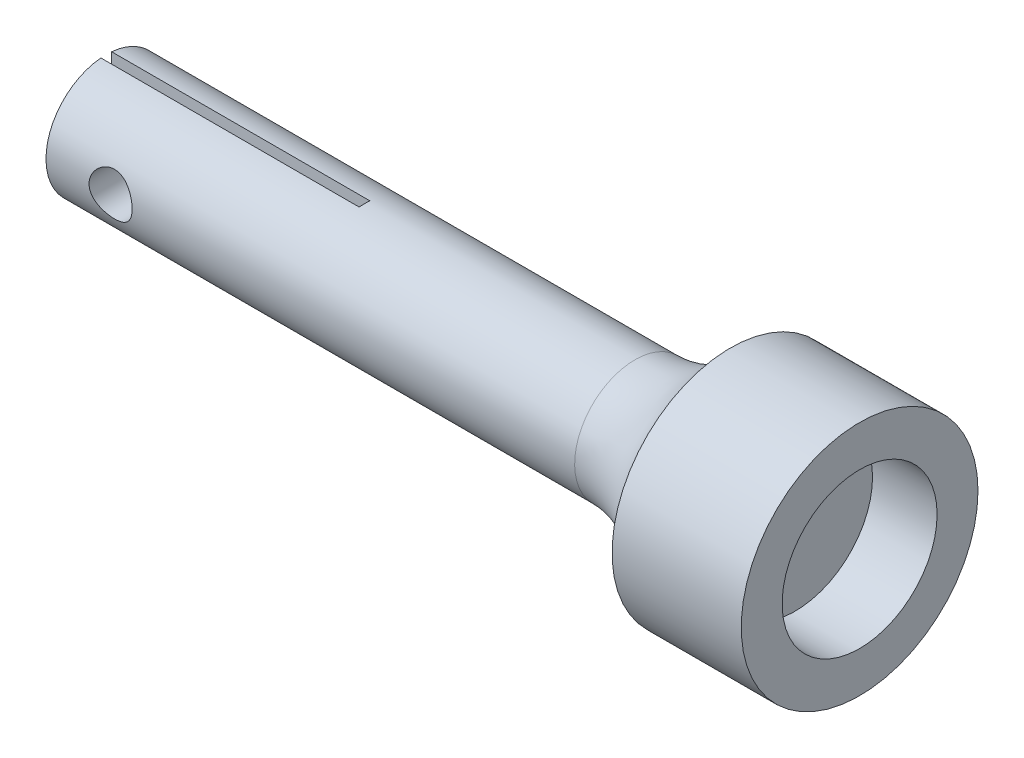
SolidWorks part; units mm, degrees
ref_plane "前视基准面" through (0, 0, 0) normal (0, 0, 1) x (1, 0, 0)
ref_plane "上视基准面" through (0, 0, 0) normal (0, 1, 0) x (1, 0, 0)
ref_plane "右视基准面" through (0, 0, 0) normal (1, 0, 0) x (0, 0, -1)
other "Configuration Table"
sketch "草图1" plane through (0, 0, 0) normal (1, 0, 0) x (0, 0, -1)
  circle A0 centre (0, 0) radius 2.8
  dimension "D1" = 5.6
extrude "凸台-拉伸1" add sketch "草图1" along normal blind 35
sketch "草图2" plane through (0, 0, 0) normal (-1, 0, 0) x (0, 0, 1)
  line L0 (0, 2.8) -> (0, -2.8) construction
  line L2 (-0.25, 3.1215) -> (0.25, 3.1215)
  line L3 (-0.25, 3.1215) -> (-0.25, -2.329)
  line L4 (-0.25, -2.329) -> (0.25, -2.329)
  line L5 (0.25, 3.1215) -> (0.25, -2.329)
  circle A0 centre (0, 0) radius 2.8 construction
  dimension "D1" = 0.5
  dimension "D2" = 0.25
extrude "切除-拉伸1" cut sketch "草图2" against normal blind 12
sketch "草图3" plane through (0, 0, 0.25) normal (0, 0, -1) x (-1, 0, 0)
  line L0 (0, -0.0056) -> (-6.0327, -0.0056) construction
  line L1 (0, -2.8) -> (0, 2.7888) construction
  circle A0 centre (-3, -0.0056) radius 1
  dimension "D1" = 2
  dimension "D2" = 3
extrude "切除-拉伸2" cut sketch "草图3" against normal blind 10 and the other way blind 10
sketch "草图4" plane through (35, 0, 0) normal (1, 0, 0) x (0, 0, -1)
  circle A0 centre (0, 0) radius 5.5
  dimension "D1" = 11
extrude "凸台-拉伸2" add sketch "草图4" against normal blind 6
sketch "草图5" plane through (35, 0, 0) normal (1, 0, 0) x (0, 0, -1)
  circle A0 centre (0, 0) radius 3.6
  dimension "D1" = 7.2
extrude "切除-拉伸3" cut sketch "草图5" against normal blind 3
fillet "圆角1" radius 5 1 edges at (29, 0, -2.8)
